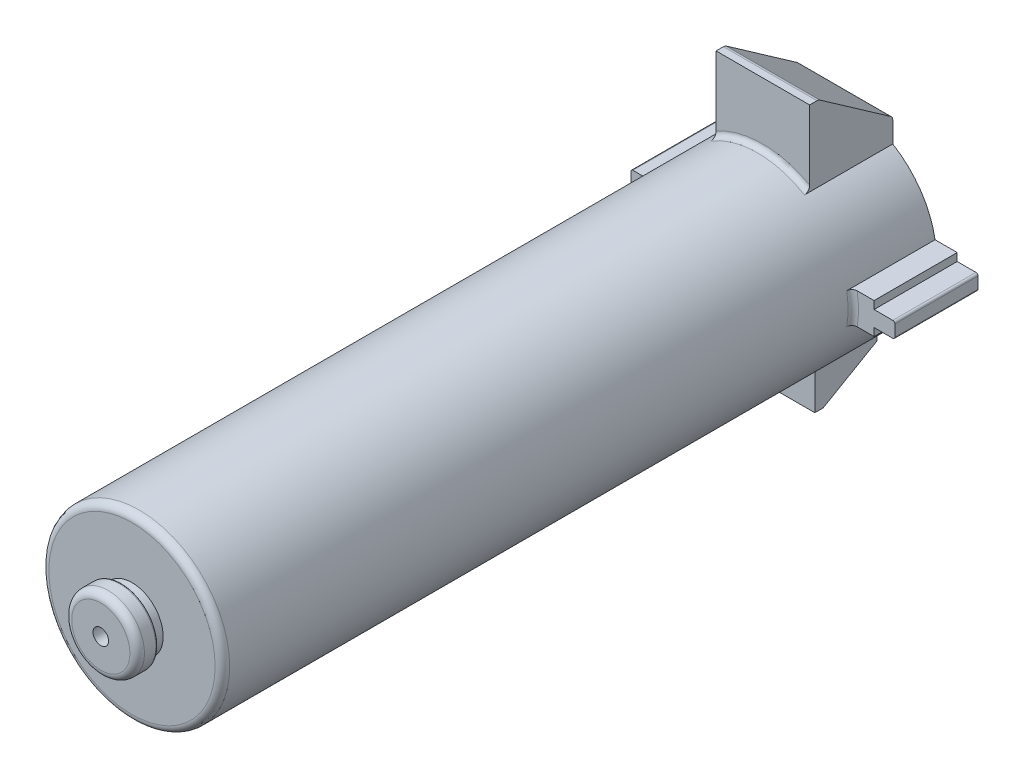
SolidWorks part; units mm, degrees
ref_plane "Спереди" through (0, 0, 0) normal (0, 0, 1) x (1, 0, 0)
ref_plane "Сверху" through (0, 0, 0) normal (0, 1, 0) x (1, 0, 0)
ref_plane "Справа" through (0, 0, 0) normal (1, 0, 0) x (0, 0, -1)
sketch "Эскиз1" plane through (0, 0, 0) normal (0, 0, 1) x (1, 0, 0)
  circle A0 centre (0, 0) radius 8.7
  dimension "D1" = 17.4
extrude "Вытянуть-Тонкостенный1" add sketch "Эскиз1" along normal blind 67 thin thin type one direction reverse wall 1.5
sketch "Эскиз3" plane through (0, 0, 67) normal (0, 0, 1) x (1, 0, 0)
  circle A0 centre (0, 0) radius 8.7
extrude "Бобышка-Вытянуть1" add sketch "Эскиз3" along normal blind 1.7
sketch "Эскиз4" plane through (0, 0, 68.7) normal (0, 0, 1) x (1, 0, 0)
  circle A0 centre (0, 0) radius 3
  dimension "D1" = 6
extrude "Бобышка-Вытянуть2" add sketch "Эскиз4" along normal blind 1
sketch "Эскиз5" plane through (0, 0, 69.7) normal (0, 0, 1) x (1, 0, 0)
  circle A0 centre (0, 0) radius 3.5
  dimension "D1" = 7
extrude "Бобышка-Вытянуть3" add sketch "Эскиз5" along normal blind 2
fillet "Скругление1" radius 0.7 1 edges at (3.5, 0, 71.7)
fillet "Скругление2" radius 0.2 1 edges at (3.5, 0, 69.7)
fillet "Скругление3" radius 0.7 1 edges at (8.7, 0, 68.7)
sketch "Эскиз6" plane through (0, 0, 0) normal (0, 0, -1) x (-1, 0, 0)
  line L1 (-4.5, 7.2) -> (4.5, 7.2)
  line L2 (-4.5, 7.2) -> (-4.5, 14.7)
  line L3 (-4.5, 14.7) -> (4.5, 14.7)
  line L4 (4.5, 7.2) -> (4.5, 14.7)
  circle A0 centre (0, 0) radius 7.2 construction
  point P4 (0, 14.7)
  point P6 (0, 0)
  point P8 (0, 0)
  dimension "D1" = 9
  dimension "D2" = 7.5
extrude "Бобышка-Вытянуть4" add sketch "Эскиз6" against normal blind 8
chamfer "Фаска1" distance 5 angle 55 1 edges at (0, 14.7, 0) first distance on face at (0, 7.0365, 0)
fillet "Скругление4" radius 0.5 2 edges at (0, 9.7, 0) (0, 14.7, 7.1407)
sketch "Эскиз7" plane through (0, 0, 0) normal (0, 0, -1) x (-1, 0, 0)
  line L1 (-3, -12.7) -> (3, -12.7)
  line L2 (-3, -12.7) -> (-3, -7.2)
  line L3 (-3, -7.2) -> (3, -7.2)
  line L4 (3, -12.7) -> (3, -7.2)
  circle A0 centre (0, 0) radius 7.2 construction
  point P6 (0, -12.7)
  dimension "D1" = 6
  dimension "D2" = 5.5
extrude "Бобышка-Вытянуть5" add sketch "Эскиз7" against normal blind 6
chamfer "Фаска2" distance 3 angle 60 1 edges at (0, -12.7, 0) first distance on face at (7.2, 0, 0)
fillet "Скругление5" radius 0.2 2 edges at (0, -12.7, 5.1962) (0, -9.7, 0)
sketch "Эскиз8" plane through (0, 0, 0) normal (0, 0, -1) x (-1, 0, 0)
  line L0 (-10.7, -0.75) -> (-10.7, -1.5)
  line L1 (-10.7, 1.5) -> (-7.2, 1.5)
  line L2 (-10.7, 1.5) -> (-10.7, 0.75)
  line L3 (-10.7, -1.5) -> (-7.2, -1.5)
  line L4 (-7.2, 1.5) -> (-7.2, -1.5)
  line L5 (-12.7, 0.75) -> (-10.7, 0.75)
  line L6 (-12.7, 0.75) -> (-12.7, -0.75)
  line L7 (-12.7, -0.75) -> (-10.7, -0.75)
  line L9 (0, 0) -> (0, 5.2131) construction
  line L10 (10.7, 1.5) -> (10.7, 0.75)
  line L11 (12.7, 0.75) -> (10.7, 0.75)
  line L12 (12.7, 0.75) -> (12.7, -0.75)
  line L13 (12.7, -0.75) -> (10.7, -0.75)
  line L14 (10.7, -0.75) -> (10.7, -1.5)
  line L15 (10.7, -1.5) -> (7.2, -1.5)
  line L16 (7.2, 1.5) -> (7.2, -1.5)
  line L17 (10.7, 1.5) -> (7.2, 1.5)
  circle A0 centre (0, 0) radius 7.2 construction
  point P8 (-12.7, 0)
  point P9 (-7.2, 0)
  dimension "D1" = 1.5
  dimension "D2" = 3
  dimension "D3" = 5.5
  dimension "D4" = 2
extrude "Бобышка-Вытянуть6" add sketch "Эскиз8" against normal blind 8
fillet "Скругление6" radius 0.2 4 edges at (-12.7, -0.75, 4) (-12.7, 0.75, 4) (12.7, -0.75, 4) (12.7, 0.75, 4)
sketch "Эскиз9" plane through (0, 0, 71.7) normal (0, 0, 1) x (1, 0, 0)
  circle A0 centre (0, 0) radius 0.75
  dimension "D1" = 1.5
extrude "Вырез-Вытянуть1" cut sketch "Эскиз9" against normal through all
fillet "Скругление7" radius 0.5 4 edges at (0, -8.7, 6) (0, 8.7, 8) (8.7, 0, 8) (-8.7, 0, 8)
